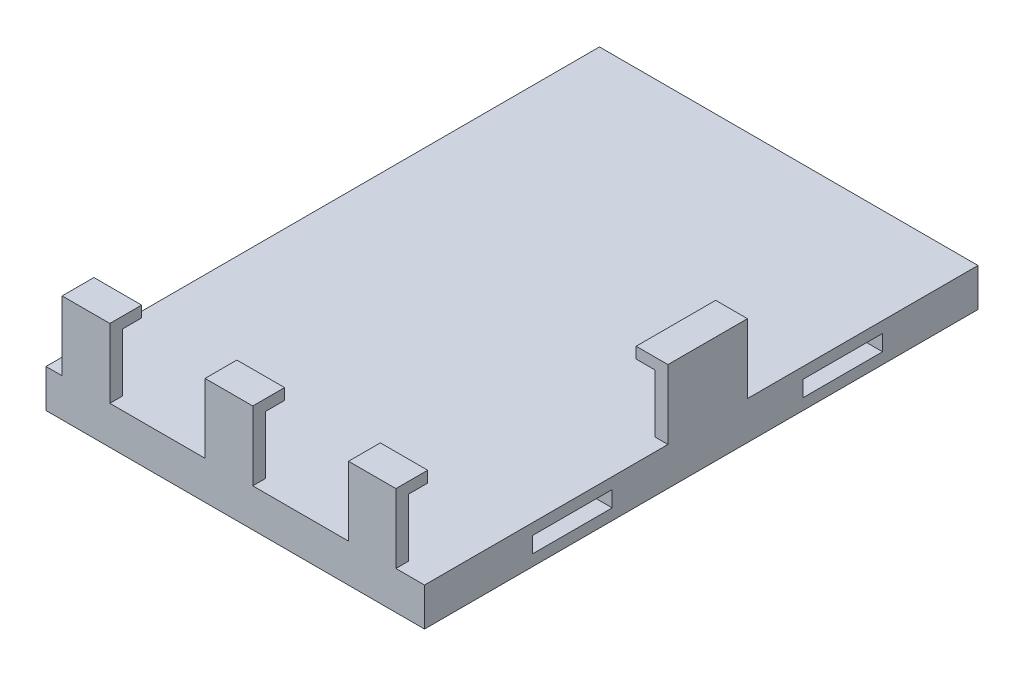
SolidWorks part; units mm, degrees
ref_plane "Front Plane" through (0, 0, 0) normal (0, 0, 1) x (1, 0, 0)
ref_plane "Top Plane" through (0, 0, 0) normal (0, 1, 0) x (1, 0, 0)
ref_plane "Right Plane" through (0, 0, 0) normal (1, 0, 0) x (0, 0, -1)
sketch "Sketch1" plane through (0, 0, 0) normal (0, 1, 0) x (1, 0, 0)
  line L1 (-29.21, -43.18) -> (29.21, -43.18)
  line L2 (-29.21, -43.18) -> (-29.21, 43.18)
  line L3 (-29.21, 43.18) -> (29.21, 43.18)
  line L4 (29.21, -43.18) -> (29.21, 43.18)
  line L5 (-29.21, -43.18) -> (29.21, 43.18) construction
  line L6 (-29.21, 43.18) -> (29.21, -43.18) construction
  point P0 (0, 0)
  dimension "D1" = 86.36
  dimension "D2" = 58.42
extrude "basePlate" add sketch "Sketch1" along normal blind 2.032
sketch "Sketch4" plane through (0, 0, 43.18) normal (0, 0, 1) x (1, 0, 0)
  line L0 (0, 0) -> (0, 2.032) construction
  line L1 (-29.21, 2.032) -> (29.21, 2.032) construction
sketch "Sketch5" plane through (0, 2.032, 0) normal (0, 1, 0) x (1, 0, 0)
  line L0 (0, 0) -> (0, -43.18) construction
  line L1 (-29.21, -43.18) -> (29.21, -43.18) construction
  line L2 (3.81, -43.18) -> (-3.81, -43.18)
  line L3 (-3.81, -43.18) -> (-3.81, -45.212)
  line L4 (-3.81, -45.212) -> (3.81, -45.212)
  line L5 (3.81, -45.212) -> (3.81, -43.18)
  line L6 (-29.21, -43.18) -> (-26.67, -43.18) construction
  line L7 (29.21, -43.18) -> (26.67, -43.18) construction
  line L8 (0, 0) -> (29.21, 0) construction
  line L9 (-26.67, -43.18) -> (-19.0139, -43.18)
  line L10 (-26.67, -43.18) -> (-26.67, -45.212)
  line L11 (-26.67, -45.212) -> (-19.0139, -45.212)
  line L12 (-19.0139, -43.18) -> (-19.0139, -45.212)
  line L13 (26.67, -43.18) -> (19.105, -43.18)
  line L14 (26.67, -43.18) -> (26.67, -45.212)
  line L15 (26.67, -45.212) -> (19.105, -45.212)
  line L16 (19.105, -43.18) -> (19.105, -45.212)
  line L17 (29.21, -43.18) -> (29.21, 43.18) construction
  line L18 (29.21, 0) -> (29.21, -6.337) construction
  line L20 (29.21, -6.337) -> (31.242, -6.337)
  line L21 (29.21, -6.337) -> (29.21, 6.363)
  line L22 (29.21, 6.363) -> (31.242, 6.363)
  line L23 (31.242, -6.337) -> (31.242, 6.363)
  dimension "D1" = 12.7
  dimension "D2" = 2.032
  dimension "D3" = 2.032
extrude "Boss-Extrude3" add sketch "Sketch5" along normal blind 9.271 separate body
extrude "Boss-Extrude4" add sketch "Sketch5<2>" against normal blind 2.032
sketch "Sketch5<2>" plane through (0, 2.032, 0) normal (0, 1, 0) x (1, 0, 0) same geometry as "Sketch5"
sketch "Sketch6" plane through (0, 0, 43.18) normal (0, 0, -1) x (-1, 0, 0)
  line L1 (-26.67, 11.303) -> (-19.105, 11.303)
  line L2 (-26.67, 11.303) -> (-26.67, 13.081)
  line L3 (-26.67, 13.081) -> (-19.105, 13.081)
  line L4 (-19.105, 11.303) -> (-19.105, 13.081)
  line L5 (-3.81, 11.303) -> (3.81, 11.303)
  line L6 (-3.81, 11.303) -> (-3.81, 13.081)
  line L7 (-3.81, 13.081) -> (3.81, 13.081)
  line L8 (3.81, 11.303) -> (3.81, 13.081)
  line L9 (19.0139, 11.303) -> (26.6339, 11.303)
  line L10 (19.0139, 11.303) -> (19.0139, 13.081)
  line L11 (19.0139, 13.081) -> (26.6339, 13.081)
  line L12 (26.6339, 11.303) -> (26.6339, 13.081)
  dimension "D1" = 1.778
  dimension "D2" = 1.778
  dimension "D3" = 1.778
  dimension "D4" = 7.62
extrude "Boss-Extrude5" add sketch "Sketch6" along normal blind 3.048 separate body
extrude "Boss-Extrude6" add sketch "Sketch6<2>" against normal up to surface (2.032 mm away) up to face at (22.8875, 5.6515, 45.212)
sketch "Sketch6<2>" plane through (0, 0, 43.18) normal (0, 0, -1) x (-1, 0, 0) same geometry as "Sketch6"
sketch "Sketch7" plane through (0, 0, 0) normal (0, -1, 0) x (1, 0, 0)
  line L1 (-19.0139, 43.18) -> (-3.81, 43.18)
  line L2 (-19.0139, 43.18) -> (-19.0139, 45.212)
  line L3 (-19.0139, 45.212) -> (-3.81, 45.212)
  line L4 (-3.81, 43.18) -> (-3.81, 45.212)
  line L5 (3.81, 43.18) -> (19.105, 43.18)
  line L6 (3.81, 43.18) -> (3.81, 45.212)
  line L7 (3.81, 45.212) -> (19.105, 45.212)
  line L8 (19.105, 43.18) -> (19.105, 45.212)
  line L9 (-29.21, 43.18) -> (-26.67, 43.18)
  line L10 (-29.21, 43.18) -> (-29.21, 45.212)
  line L11 (-29.21, 45.212) -> (-26.67, 45.212)
  line L12 (-26.67, 43.18) -> (-26.67, 45.212)
  line L13 (29.21, 43.18) -> (26.67, 43.18)
  line L15 (29.21, 45.212) -> (26.67, 45.212)
  line L16 (26.67, 43.18) -> (26.67, 45.212)
  line L17 (31.242, 6.337) -> (29.21, 6.337)
  line L18 (31.242, 6.337) -> (31.242, 45.212)
  line L19 (31.242, 45.212) -> (29.21, 45.212)
  line L20 (29.21, 6.337) -> (29.21, 43.18)
  line L21 (31.242, -6.363) -> (29.21, -6.363)
  line L22 (31.242, -6.363) -> (31.242, -43.18)
  line L23 (31.242, -43.18) -> (29.21, -43.18)
  line L24 (29.21, -6.363) -> (29.21, -43.18)
extrude "Boss-Extrude7" add sketch "Sketch7" against normal up to surface (2.032 mm away) up to face at (4.8759, 2.032, 21.5878)
sketch "Sketch9" plane through (29.21, 0, 0) normal (-1, 0, 0) x (0, 0, 1)
  line L1 (-6.363, 11.303) -> (6.337, 11.303)
  line L2 (-6.363, 11.303) -> (-6.363, 13.081)
  line L3 (-6.363, 13.081) -> (6.337, 13.081)
  line L4 (6.337, 11.303) -> (6.337, 13.081)
  dimension "D1" = 1.778
extrude "Boss-Extrude8" add sketch "Sketch9" along normal blind 3.048 separate body
extrude "Boss-Extrude9" add sketch "Sketch9<2>" against normal up to surface (2.032 mm away) up to face at (31.242, 3.8417, 0.5015)
sketch "Sketch9<2>" plane through (29.21, 0, 0) normal (-1, 0, 0) x (0, 0, 1) same geometry as "Sketch9"
sketch "Sketch11" plane through (0, 0, 0) normal (0, -1, 0) x (1, 0, 0)
  line L1 (-29.21, 45.212) -> (31.242, 45.212)
  line L2 (-29.21, 45.212) -> (-29.21, -43.18)
  line L3 (-29.21, -43.18) -> (31.242, -43.18)
  line L4 (31.242, 45.212) -> (31.242, -43.18)
extrude "Boss-Extrude10" add sketch "Sketch11" along normal blind 4.064
sketch "Sketch12" plane through (-29.21, 0, 0) normal (-1, 0, 0) x (0, 0, 1)
  line L0 (21.59, -1.016) -> (-21.59, -1.016) construction
  line L1 (45.212, -4.064) -> (-43.18, -4.064) construction
  line L2 (0, -4.064) -> (0, 2.032) construction
  line L3 (-43.18, 2.032) -> (45.212, 2.032) construction
  line L4 (27.94, 0.254) -> (15.24, -2.286) construction
  line L5 (-27.94, -2.286) -> (-15.24, -2.286)
  line L6 (-27.94, -2.286) -> (-27.94, 0.254)
  line L7 (-27.94, 0.254) -> (-15.24, 0.254)
  line L8 (-15.24, -2.286) -> (-15.24, 0.254)
  line L9 (-27.94, -2.286) -> (-15.24, 0.254) construction
  line L10 (-27.94, 0.254) -> (-15.24, -2.286) construction
  line L11 (27.94, -2.286) -> (15.24, 0.254) construction
  line L12 (15.24, -2.286) -> (15.24, 0.254)
  line L13 (27.94, 0.254) -> (15.24, 0.254)
  line L14 (27.94, -2.286) -> (27.94, 0.254)
  line L15 (27.94, -2.286) -> (15.24, -2.286)
  point P10 (0, -1.016)
  dimension "D1" = 2.54
  dimension "D2" = 12.7
extrude "Cut-Extrude1" cut sketch "Sketch12" against normal through all
